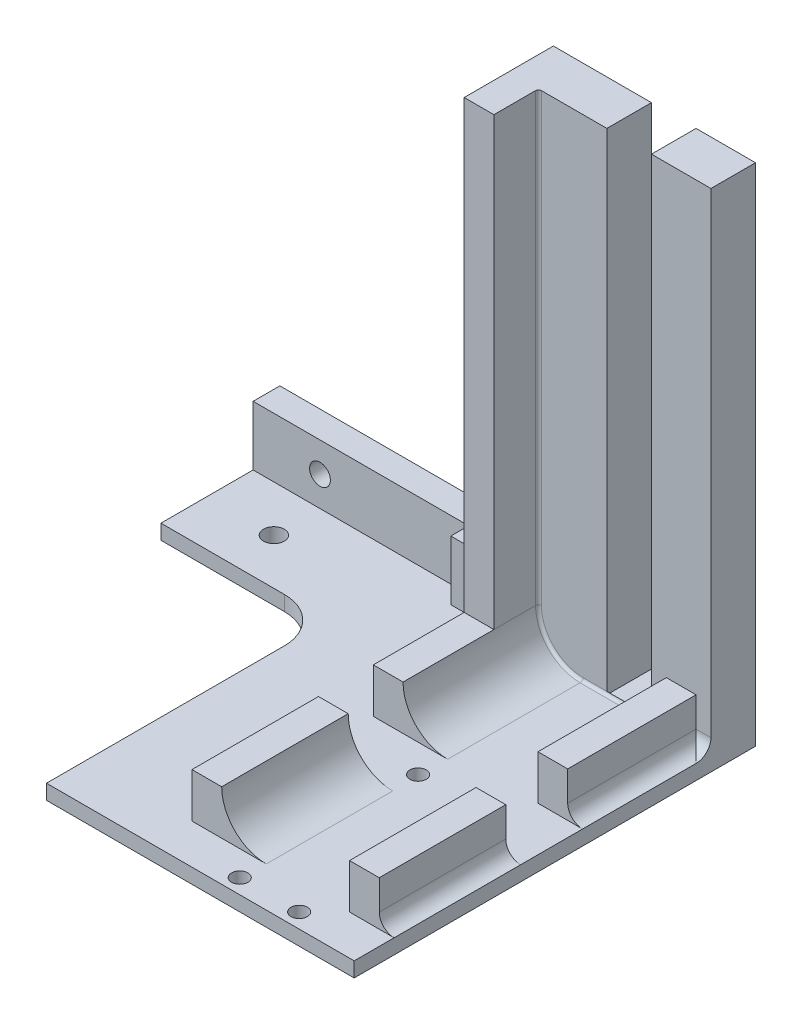
SolidWorks part; units mm, degrees
ref_plane "Front Plane" through (0, 0, 0) normal (0, 0, 1) x (1, 0, 0)
ref_plane "Top Plane" through (0, 0, 0) normal (0, 1, 0) x (1, 0, 0)
ref_plane "Right Plane" through (0, 0, 0) normal (1, 0, 0) x (0, 0, -1)
sketch "profile" plane through (0, 0, 0) normal (0, 0, 1) x (1, 0, 0)
  line L0 (11.8803, 7.4874) -> (14.5, 7.4874)
  line L1 (-5.5, 6.9749) -> (-7.8749, 4.6)
  line L2 (-7.8749, 4.6) -> (-12.1251, 4.6)
  line L3 (-12.1251, 4.6) -> (-14.5, 6.9749)
  line L4 (-8.1197, 7.4874) -> (-5.5, 7.4874)
  line L5 (-14.5, 6.9749) -> (-15.0126, 7.4874)
  line L6 (14.5, 6.9749) -> (12.1251, 4.6)
  line L7 (12.1251, 4.6) -> (7.8749, 4.6)
  line L8 (7.8749, 4.6) -> (5.5, 6.9749)
  line L9 (-14.7464, 10.3536) -> (-5.2536, 10.3536)
  line L10 (-14.5, 7.4874) -> (-11.8803, 7.4874)
  line L11 (5.5, 7.4874) -> (8.5334, 7.4874)
  line L12 (5.6673, 10.3536) -> (14.7464, 10.3536)
  line L13 (-15.0126, 7.4874) -> (-14.5, 7.4874)
  line L14 (-5.5, 6.9749) -> (-4.9874, 7.4874)
  line L15 (-4.9874, 7.4874) -> (-5.5, 7.4874)
  line L16 (5.5, 6.9749) -> (4.9874, 7.4874)
  line L17 (4.9874, 7.4874) -> (5.5, 7.4874)
  line L18 (14.5, 6.9749) -> (15.0126, 7.4874)
  line L19 (15.0126, 7.4874) -> (14.5, 7.4874)
  line L20 (-12.7464, 8.3536) -> (-14.7464, 10.3536)
  line L21 (-5.2536, 10.3536) -> (-7.2536, 8.3536)
  line L22 (7.6673, 8.3536) -> (5.6673, 10.3536)
  line L23 (14.7464, 10.3536) -> (12.7464, 8.3536)
  line L24 (-12.7464, 8.3536) -> (-11.8803, 7.4874)
  line L25 (-7.2536, 8.3536) -> (-8.1197, 7.4874)
  line L26 (7.6673, 8.3536) -> (8.5334, 7.4874)
  line L27 (12.7464, 8.3536) -> (11.8803, 7.4874)
  line L28 (-14.7464, 10.3536) -> (-20, 10.3536)
  line L29 (-20, 10.3536) -> (-20, 15.3536)
  line L30 (-20, 15.3536) -> (20, 15.3536)
  line L31 (20, 15.3536) -> (20, 10.3536)
  line L32 (20, 10.3536) -> (14.7464, 10.3536)
  line L33 (-5.2536, 10.3536) -> (5.6673, 10.3536)
  point P0 (-10, 4.6)
  point P1 (10, 4.6)
  dimension "D1" = 4.2503
  dimension "D2" = 5.7536
  dimension "D3" = 15.7497
  dimension "D4" = 20
  dimension "D5" = 5
extrude "Boss-Extrude1" add sketch "profile" along normal blind 250 contours L9 L33 L12 L32 L31 L30 L29 L28 region at (0, 12.8536, 0)
extrude "Boss-Extrude2" add sketch "Sketch1<3>" along normal blind 50 separate body contours L25 L21 L9 L20 L24 L10 L13 L5 L3 L2 L1 L14 L15 L4 | L27 L23 L12 L22 L26 L11 L17 L16 L8 L7 L6 L18 L19 L0 region at (10.0959, 7.5838, 0) region at (-10, 7.6238, 0)
sketch "Sketch1<3>" plane through (0, 0, 0) normal (0, 0, 1) x (1, 0, 0) same geometry as "profile"
pattern_linear "LPattern1" count 4 spacing 60 along (0, 0, 1) of "Boss-Extrude2"
sketch "Sketch2" plane through (0, 10.3536, 0) normal (0, -1, 0) x (1, 0, 0)
  line L0 (10, 250) -> (10, 0) construction
  line L1 (-20, 250) -> (20, 250) construction
  line L2 (12.1251, 0) -> (7.8749, 0) construction
  line L3 (-10, 230) -> (-10, 0) construction
  line L4 (-7.8749, 230) -> (-12.1251, 230) construction
  line L5 (-7.8749, 0) -> (-12.1251, 0) construction
  line L6 (-7.8749, 180) -> (-7.8749, 170) construction
  line L7 (-7.8749, 180) -> (-12.1251, 180) construction
  circle A0 centre (-10, 175) radius 2.75
  circle A1 centre (10, 175) radius 2.75
  circle A2 centre (-10, 115) radius 2.75
  circle A3 centre (10, 115) radius 2.75
  circle A4 centre (-10, 55) radius 2.75
  circle A5 centre (10, 55) radius 2.75
  point P21 (-7.8749, 175)
  dimension "D1" = 5.5
  dimension "D2" = 3
extrude "Cut-Extrude1" cut sketch "Sketch2" against normal through all
sketch "upper_acrylic_supp" plane through (0, 15.3536, 0) normal (0, 1, 0) x (1, 0, 0)
  line L0 (-20, 0) -> (20, 0) construction
  line L1 (-20, -250) -> (-34.5, -250) construction
  line L2 (-20, -250) -> (-20, 0) construction
  line L3 (-20, 0) -> (-34.5, 0) construction
  line L4 (-34.5, -250) -> (-34.5, 0) construction
  line L6 (-34.5, -250) -> (-24.5, -250)
  line L7 (-34.5, -250) -> (-34.5, -183.9264)
  line L8 (-34.5, -183.9264) -> (-24.5, -183.9264)
  line L9 (-24.5, -250) -> (-24.5, -183.9264)
  line L10 (-34.5, -165.3527) -> (-24.5, -165.3527)
  line L11 (-34.5, -165.3527) -> (-34.5, -123.8775)
  line L12 (-34.5, -123.8775) -> (-24.5, -123.8775)
  line L13 (-24.5, -165.3527) -> (-24.5, -123.8775)
  line L14 (-34.5, -106.5661) -> (-24.5, -106.5661)
  line L15 (-34.5, -106.5661) -> (-34.5, -64.0089)
  line L16 (-34.5, -64.0089) -> (-24.5, -64.0089)
  line L17 (-24.5, -106.5661) -> (-24.5, -64.0089)
  line L18 (-34.5, -45.5583) -> (-24.5, -45.5583)
  line L19 (-34.5, -45.5583) -> (-34.5, 0)
  line L20 (-34.5, 0) -> (-24.5, 0)
  line L21 (-24.5, -45.5583) -> (-24.5, 0)
  line L22 (-20, -250) -> (-40, -250)
  line L23 (-20, -250) -> (-20, 0)
  line L24 (-20, 0) -> (-40, 0)
  line L25 (-40, -250) -> (-40, 0)
  line M21 (-20, 0) -> (-20, -250)
  dimension "D1" = 5.5
  dimension "D2" = 10
  dimension "D3" = 20
extrude "Boss-Extrude3" add sketch "upper_acrylic_supp" against normal blind 5 contours L25 L22 L24 L21 L18 L19 L17 L14 L15 L16 L13 L10 L11 L12 L9 L6 L7 L8 M21 | L14 L17 L16 L15 | L10 L13 L12 L11 | L6 L9 L8 L7 | L18 L21 L20 L19 region at (-29.5, 15.3536, 216.9632) region at (-30.3215, 15.3536, 123.2164) region at (-29.5, 15.3536, 22.7792) region at (-29.5, 15.3536, 144.6151) region at (-29.5, 15.3536, 85.2875)
extrude "Boss-Extrude4" add sketch "upper_acrylic_supp<3>" along normal blind 15 contours L6 L9 L8 L7 | L10 L13 L12 L11 | L14 L17 L16 L15 | L18 L21 L20 L19 region at (-29.5, 15.3536, 216.9632) region at (-29.5, 15.3536, 22.7792) region at (-29.5, 15.3536, 144.6151) region at (-29.5, 15.3536, 85.2875)
sketch "upper_acrylic_supp<3>" plane through (0, 15.3536, 0) normal (0, 1, 0) x (1, 0, 0) same geometry as "upper_acrylic_supp"
fillet "Fillet1" radius 15 4 edges at (-24.5, 15.3536, 22.7792) (-24.5, 15.3536, 85.2875) (-24.5, 15.3536, 144.6151) (-24.5, 15.3536, 216.9632)
sketch "Sketch4" plane through (0, 15.3536, 0) normal (0, 1, 0) x (1, 0, 0)
  line L0 (20, -250) -> (20, 0) construction
  line L1 (-40, -250) -> (20, -250)
  line L2 (-40, -250) -> (-40, -265)
  line L3 (-40, -265) -> (20, -265)
  line L4 (20, -250) -> (20, -265)
  line L5 (-40, 0) -> (20, 0)
  line L6 (-40, 0) -> (-40, 15)
  line L7 (-40, 15) -> (20, 15)
  line L8 (20, 0) -> (20, 15)
  line L10 (-34.5, -265) -> (-34.5, 15) construction
  dimension "D1" = 15
  dimension "D2" = 15
extrude "Boss-Extrude5" add sketch "Sketch4" along normal mid plane 10
extrude "Boss-Extrude6" add sketch "Sketch4<3>" along normal blind 60
sketch "Sketch4<3>" plane through (0, 15.3536, 0) normal (0, 1, 0) x (1, 0, 0) same geometry as "Sketch4"
sketch "Sketch5" plane through (0, 0, 250) normal (0, 0, -1) x (-1, 0, 0)
  line L0 (-20, 75.3536) -> (40, 75.3536) construction
  line L1 (40, 15.3536) -> (34.5, 15.3536)
  line L2 (40, 15.3536) -> (40, 75.3536)
  line L3 (40, 75.3536) -> (34.5, 75.3536)
  line L4 (34.5, 15.3536) -> (34.5, 75.3536)
  line L6 (34.5, 15.3536) -> (24.5, 15.3536)
  line L7 (34.5, 15.3536) -> (34.5, 75.3536)
  line L8 (34.5, 75.3536) -> (24.5, 75.3536)
  line L9 (24.5, 15.3536) -> (24.5, 75.3536)
  line M5 (40, 75.3536) -> (-20, 75.3536)
  line M9 (24.5, 30.3536) -> (34.5, 30.3536)
  dimension "D1" = 5.5
  dimension "D2" = 10
extrude "Boss-Extrude7" add sketch "Sketch5" along normal blind 15 contours L9 L4 M9 M5 region at (-29.5, 52.8536, 250)
extrude "Boss-Extrude8" add sketch "Sketch5<3>" against normal blind 15 from surface contours L9 L4 M9 M5 region at (-29.5, 52.8536, 250) starting at face at (-18.2633, 33.7152, 0)
sketch "Sketch5<3>" plane through (0, 0, 250) normal (0, 0, -1) x (-1, 0, 0) same geometry as "Sketch5"
fillet "Fillet2" radius 1 6 edges at (5.25, 15.3536, 0) (-20.1066, 19.747, 0) (5.25, 15.3536, 250) (-20.1066, 19.747, 250) (-24.5, 52.8536, 0) (-24.5, 52.8536, 250)
sketch "Sketch6" plane through (-40, 0, 0) normal (-1, 0, 0) x (0, 0, 1)
  line L1 (250, 15.3536) -> (256, 15.3536)
  line L2 (250, 15.3536) -> (250, 75.3536)
  line L3 (250, 75.3536) -> (256, 75.3536)
  line L4 (256, 15.3536) -> (256, 75.3536)
  line L6 (0, 15.3536) -> (-6, 15.3536)
  line L7 (0, 15.3536) -> (0, 75.3536)
  line L8 (0, 75.3536) -> (-6, 75.3536)
  line L9 (-6, 15.3536) -> (-6, 75.3536)
  dimension "D1" = 6
  dimension "D2" = 6
extrude "Cut-Extrude2" cut sketch "Sketch6" against normal blind 6
sketch "Sketch7" plane through (-40, 0, 0) normal (-1, 0, 0) x (0, 0, 1)
  line L8 (265, 75.3536) -> (256, 75.3536)
  line L9 (256, 75.3536) -> (256, 15.3536)
  line L10 (256, 15.3536) -> (-6, 15.3536)
  line L11 (-6, 15.3536) -> (-6, 75.3536)
  line L12 (-6, 75.3536) -> (-15, 75.3536)
  line L13 (-15, 75.3536) -> (-15, 10.3536)
  line L14 (-15, 10.3536) -> (265, 10.3536)
  line L15 (265, 10.3536) -> (265, 75.3536)
  line L16 (265, 75.3536) -> (256, 75.3536)
  line L17 (256, 75.3536) -> (256, 15.3536)
  line L18 (256, 15.3536) -> (-6, 15.3536)
  line L19 (-6, 15.3536) -> (-6, 75.3536)
  line L20 (-6, 75.3536) -> (-15, 75.3536)
  line L21 (-15, 75.3536) -> (-15, 10.3536)
  line L22 (-15, 10.3536) -> (265, 10.3536)
  line L23 (265, 10.3536) -> (265, 75.3536)
  dimension "D1" = 0
extrude "Boss-Extrude9" add sketch "Sketch7" along normal blind 30
sketch "Sketch8" plane through (-70, 0, 0) normal (-1, 0, 0) x (0, 0, 1)
  line L0 (-15, 10.3536) -> (265, 10.3536) construction
  line L1 (-44.3745, 35.3536) -> (289.2282, 35.3536)
  line L2 (-44.3745, 35.3536) -> (-44.3745, 94.3849)
  line L3 (-44.3745, 94.3849) -> (289.2282, 94.3849)
  line L4 (289.2282, 35.3536) -> (289.2282, 94.3849)
  dimension "D1" = 25
extrude "Cut-Extrude3" cut sketch "Sketch8" against normal blind 150
sketch "Sketch9" plane through (-34, 0, 0) normal (-1, 0, 0) x (0, 0, 1)
  line L4 (256, 15.3536) -> (256, 35.3536)
  line L5 (256, 35.3536) -> (250, 35.3536)
  line L6 (250, 35.3536) -> (250, 15.3536)
  line L7 (250, 15.3536) -> (256, 15.3536)
  line L8 (256, 15.3536) -> (256, 35.3536)
  line L9 (256, 35.3536) -> (250, 35.3536)
  line L10 (250, 35.3536) -> (250, 15.3536)
  line L11 (250, 15.3536) -> (256, 15.3536)
  line L12 (0, 35.3536) -> (-6, 35.3536)
  line L13 (-6, 35.3536) -> (-6, 15.3536)
  line L14 (-6, 15.3536) -> (0, 15.3536)
  line L15 (0, 15.3536) -> (0, 35.3536)
  line L16 (0, 35.3536) -> (-6, 35.3536)
  line L17 (-6, 35.3536) -> (-6, 15.3536)
  line L18 (-6, 15.3536) -> (0, 15.3536)
  line L19 (0, 15.3536) -> (0, 35.3536)
  dimension "D1" = 0
  dimension "D2" = 0
extrude "cloth_escape_gap" add sketch "Sketch9" along normal blind 20
sketch "Sketch11" plane through (-70, 0, 0) normal (-1, 0, 0) x (0, 0, 1)
  line L0 (256, 35.3536) -> (256, 15.3536) construction
  line L1 (-15, 35.3536) -> (-6, 35.3536)
  line L2 (-15, 35.3536) -> (-15, 15.3536)
  line L3 (-15, 15.3536) -> (-6, 15.3536)
  line L4 (-6, 35.3536) -> (-6, 15.3536)
  line L5 (265, 35.3536) -> (256, 35.3536)
  line L6 (265, 35.3536) -> (265, 15.3536)
  line L7 (265, 15.3536) -> (256, 15.3536)
  line L8 (256, 35.3536) -> (256, 15.3536)
  line L9 (256, 15.3536) -> (256, 35.3536) construction
extrude "Boss-Extrude11" add sketch "Sketch11" along normal blind 100
sketch "Sketch12" plane through (0, 10.3536, 0) normal (0, -1, 0) x (1, 0, 0)
  line L0 (-70, -15) -> (-170, -10.5)
  line L1 (-170, -15) -> (-170, -6) construction
  line L2 (-170, -10.5) -> (-170, -15)
  line L3 (-170, -15) -> (-70, -15) construction
  line L4 (-170, -15) -> (-70, -15)
  line L5 (-70, 265) -> (-170, 260.5)
  line L6 (-170, 256) -> (-170, 265) construction
  line L7 (-170, 260.5) -> (-170, 265)
  line L8 (-170, 265) -> (-70, 265)
extrude "Cut-Extrude4" cut sketch "Sketch12" against normal blind 68 contours L8 L7 L5 | L0 L2 L4 region at (-136.6667, 10.3536, 263.5)
sketch "Sketch13" plane through (-70, 0, 0) normal (-1, 0, 0) x (0, 0, 1)
  line L0 (256, 15.3536) -> (265, 15.3536) construction
  line L1 (-15, 10.3536) -> (25, 10.3536)
  line L2 (-15, 10.3536) -> (-15, 15.3536)
  line L3 (-15, 15.3536) -> (25, 15.3536)
  line L4 (25, 10.3536) -> (25, 15.3536)
  line L5 (265, 10.3536) -> (225, 10.3536)
  line L6 (265, 10.3536) -> (265, 15.3536)
  line L7 (265, 15.3536) -> (225, 15.3536)
  line L8 (225, 10.3536) -> (225, 15.3536)
  line L9 (256, 15.3536) -> (-6, 15.3536) construction
  dimension "D1" = 40
  dimension "D2" = 40
extrude "Boss-Extrude13" add sketch "Sketch13" along normal blind 100
sketch "Sketch14" plane through (0, 15.3536, 0) normal (0, 1, 0) x (1, 0, 0)
  line L3 (-70, -265) -> (-170, -260.5)
  line L4 (-170, -260.5) -> (-170, -265)
  line L5 (-170, -265) -> (-70, -265)
  line L6 (-70, -265) -> (-170, -260.5)
  line L7 (-170, -260.5) -> (-170, -265)
  line L8 (-170, -265) -> (-70, -265)
  line L9 (-170, 15) -> (-170, 10.5)
  line L10 (-170, 10.5) -> (-70, 15)
  line L11 (-70, 15) -> (-170, 15)
  line L12 (-170, 15) -> (-170, 10.5)
  line L13 (-170, 10.5) -> (-70, 15)
  line L14 (-70, 15) -> (-170, 15)
  dimension "D1" = 0
  dimension "D2" = 0
extrude "Cut-Extrude5" cut sketch "Sketch14" against normal blind 100
fillet "Fillet3" radius 15 2 edges at (-70, 12.8536, 25) (-70, 12.8536, 225)
sketch "Sketch16" plane through (0, 15.3536, 0) normal (0, 1, 0) x (1, 0, 0)
  line L0 (20, -1) -> (-9.5, -1) construction
  line L1 (-34.5, -235) -> (18.5, -235) construction
  line L2 (-34.5, -235) -> (-34.5, -1) construction
  line L3 (-34.5, -1) -> (18.5, -1) construction
  line L4 (18.5, -235) -> (18.5, -1) construction
  line L5 (20, -265) -> (-70, -265) construction
  line L6 (18.5, -265) -> (33.5, -265)
  line L7 (18.5, -265) -> (18.5, 15)
  line L8 (18.5, 15) -> (33.5, 15)
  line L9 (33.5, -265) -> (33.5, 15)
  line L10 (-70, 15) -> (20, 15) construction
  line L11 (18.5, -250) -> (33.5, -250)
  line L12 (18.5, 0) -> (33.5, 0)
  line L13 (-23.5, -250) -> (20, -250) construction
  line L14 (-9.5, 0) -> (20, 0) construction
  line L15 (18.5, -250) -> (28.5, -250)
  line L16 (28.5, -250) -> (28.5, -183.9264)
  line L17 (28.5, 0) -> (18.5, 0)
  line L18 (18.5, -183.9264) -> (28.5, -183.9264)
  line L19 (18.5, -165.3527) -> (28.5, -165.3527)
  line L20 (18.5, -123.8775) -> (28.5, -123.8775)
  line L21 (18.5, -106.5661) -> (28.5, -106.5661)
  line L22 (18.5, -64.0089) -> (28.5, -64.0089)
  line L23 (18.5, -43.1778) -> (28.5, -43.1778)
  line L24 (-34.5, -165.3527) -> (-9.5, -165.3527) construction
  line L25 (-34.5, -183.9264) -> (-9.5, -183.9264) construction
  line L26 (-34.5, -106.5661) -> (-9.5, -106.5661) construction
  line L27 (-34.5, -123.8775) -> (-9.5, -123.8775) construction
  line L28 (-9.5, -64.0089) -> (-24.5, -64.0089) construction
  line L30 (28.5, -165.3527) -> (28.5, -123.8775)
  line L31 (28.5, -106.5661) -> (28.5, -64.0089)
  line L32 (28.5, -43.1778) -> (28.5, 0)
  line M38 (-9.5, -249) -> (20, -249)
  line M39 (20, -249) -> (20, -1)
  line M40 (20, -1) -> (-9.5, -1)
  dimension "D1" = 53
  dimension "D2" = 15
  dimension "D3" = 10
extrude "Boss-Extrude14" add sketch "Sketch16" along direction (0, -1, 0) on the side of the normal up to surface (20 mm away) from surface contours L7 L12 L9 L8 | L11 L7 L6 L9 region at (26, 15.3536, 257.5) region at (26, 15.3536, -7.5) up to face at (-51.6423, 35.3536, 251.8089) starting at face at (-10, 10.3536, 25)
extrude "Cut-Extrude6" cut sketch "Sketch16<5>" against normal blind 10 and the other way blind 30 contours L11 L7 L6 L9 | L32 L23 L22 L31 L21 L20 L30 L19 L18 L16 L11 L9 L12 M39 | L19 L30 L20 M39 | L21 L31 L22 M39 | L23 L32 L12 L7 M40 M39 | L7 L12 L9 L8 | L7 L23 M39 M40 | L23 L7 L22 M39 | L22 L7 L21 M39 | L21 L7 L20 M39 | L20 L7 L19 M39 | L19 L7 L18 M39 | L18 L7 M38 M39 | L18 L7 L11 L16 M39 M38 region at (26, 15.3536, 257.5) region at (24.2367, 15.3536, 217.0499) region at (29.1213, 15.3536, 121.3942) region at (19.25, 15.3536, 216.4632) region at (26, 15.3536, -7.5) region at (19.25, 15.3536, 174.6396) region at (24.2296, 15.3536, 21.5031) region at (19.25, 15.3536, 144.6151) region at (19.25, 15.3536, 115.2218) region at (24.25, 15.3536, 144.6151) region at (19.25, 15.3536, 22.0889) region at (19.25, 15.3536, 53.5934) region at (19.25, 15.3536, 85.2875) region at (24.25, 15.3536, 85.2875)
sketch "Sketch16<5>" plane through (0, 15.3536, 0) normal (0, 1, 0) x (1, 0, 0) same geometry as "Sketch16"
extrude "Boss-Extrude15" add sketch "Sketch16<6>" against normal up to surface (5 mm away) contours L32 L23 L22 L31 L21 L20 L30 L19 L18 L16 L11 L9 L12 M39 | L18 L7 L11 L16 M39 M38 | L11 L7 L6 L9 | L19 L30 L20 M39 | L21 L31 L22 M39 | L23 L32 L12 L7 M40 M39 | L7 L12 L9 L8 | L7 L23 M39 M40 | L23 L7 L22 M39 | L22 L7 L21 M39 | L21 L7 L20 M39 | L20 L7 L19 M39 | L19 L7 L18 M39 | L18 L7 M38 M39 region at (26, 15.3536, 257.5) region at (24.2367, 15.3536, 217.0499) region at (29.1213, 15.3536, 121.3942) region at (19.25, 15.3536, 216.4632) region at (26, 15.3536, -7.5) region at (19.25, 15.3536, 174.6396) region at (24.2296, 15.3536, 21.5031) region at (19.25, 15.3536, 144.6151) region at (19.25, 15.3536, 115.2218) region at (24.25, 15.3536, 144.6151) region at (19.25, 15.3536, 22.0889) region at (19.25, 15.3536, 53.5934) region at (19.25, 15.3536, 85.2875) region at (24.25, 15.3536, 85.2875) up to face at (-90.5656, 10.3536, 125)
sketch "Sketch16<6>" plane through (0, 15.3536, 0) normal (0, 1, 0) x (1, 0, 0) same geometry as "Sketch16"
extrude "Boss-Extrude16" add sketch "Sketch16<7>" along normal up to surface (20 mm away) contours L11 L7 L6 L9 | L7 L12 L9 L8 region at (26, 15.3536, 257.5) region at (26, 15.3536, -7.5) up to face at (-51.8923, 35.3536, 251.8089)
sketch "Sketch16<7>" plane through (0, 15.3536, 0) normal (0, 1, 0) x (1, 0, 0) same geometry as "Sketch16"
extrude "Boss-Extrude17" add sketch "Sketch16<8>" along normal up to surface (15 mm away) contours L18 L7 L11 L16 M39 M38 | L19 L30 L20 M39 | L21 L31 L22 M39 | L23 L32 L12 L7 M40 M39 | L7 L23 M39 M40 | L22 L7 L21 M39 | L20 L7 L19 M39 | L18 L7 M38 M39 region at (24.2367, 15.3536, 217.0499) region at (19.25, 15.3536, 216.4632) region at (24.2296, 15.3536, 21.5031) region at (19.25, 15.3536, 144.6151) region at (24.25, 15.3536, 144.6151) region at (19.25, 15.3536, 22.0889) region at (19.25, 15.3536, 85.2875) region at (24.25, 15.3536, 85.2875) up to face at (-29.5, 30.3536, 209.4632)
sketch "Sketch16<8>" plane through (0, 15.3536, 0) normal (0, 1, 0) x (1, 0, 0) same geometry as "Sketch16"
extrude "Boss-Extrude18" add sketch "Sketch14<2>" along normal up to surface (20 mm away) and the other way up to surface (5 mm away) up to face at (-49.3923, 35.3536, -1.8089) other way up to face at (-88.0656, 10.3536, 125)
sketch "Sketch14<2>" plane through (0, 15.3536, 0) normal (0, 1, 0) x (1, 0, 0) same geometry as "Sketch14"
fillet "Fillet4" radius 5 6 edges at (31, 15.3536, 250) (31, 15.3536, 0) (28.5, 15.3536, 21.5889) (28.5, 15.3536, 85.2875) (28.5, 15.3536, 144.6151) (28.5, 15.3536, 216.9632)
sketch "Sketch18" plane through (0, 35.3536, 0) normal (0, 1, 0) x (1, 0, 0)
  line L2 (-34.5, -250) -> (-34.5, -265)
  line L3 (-34.5, 15) -> (-34.5, 0)
  line L12 (-23.5, 0) -> (33.5, 0)
  line L13 (33.5, 0) -> (33.5, 15)
  line L14 (33.5, 15) -> (-170, 15)
  line L15 (-170, 15) -> (-170, 6)
  line L30 (-170, 6) -> (-54, 6)
  line L32 (-54, 6) -> (-54, 0)
  line L38 (-54, 0) -> (-34.5, 0)
  line L39 (-34.5, 0) -> (-34.5, -15)
  line L50 (-34.5, -15) -> (-24.5, -15)
  line L51 (-24.5, -15) -> (-24.5, -1)
  line L52 (-23.5, 0) -> (33.5, 0)
  line L53 (33.5, 0) -> (33.5, 15)
  line L54 (33.5, 15) -> (-34.5, 15)
  line L59 (-34.5, 0) -> (-34.5, -15)
  line L60 (-34.5, -15) -> (-24.5, -15)
  line L61 (-24.5, -15) -> (-24.5, -1)
  line L62 (-170, -265) -> (33.5, -265)
  line L63 (33.5, -265) -> (33.5, -250)
  line L64 (33.5, -250) -> (-23.5, -250)
  line L65 (-24.5, -249) -> (-24.5, -235)
  line L66 (-24.5, -235) -> (-34.5, -235)
  line L67 (-34.5, -235) -> (-34.5, -250)
  line L68 (-34.5, -250) -> (-54, -250)
  line L69 (-54, -250) -> (-54, -256)
  line L70 (-54, -256) -> (-170, -256)
  line L71 (-170, -256) -> (-170, -265)
  line L72 (-34.5, -265) -> (33.5, -265)
  line L73 (33.5, -265) -> (33.5, -250)
  line L74 (33.5, -250) -> (-23.5, -250)
  line L75 (-24.5, -249) -> (-24.5, -235)
  line L76 (-24.5, -235) -> (-34.5, -235)
  line L77 (-34.5, -235) -> (-34.5, -250)
  arc A5 (-23.5, 0) -> (-24.5, -1) centre (-23.5, -1) ccw
  arc A6 (-23.5, 0) -> (-24.5, -1) centre (-23.5, -1) ccw
  arc A7 (-24.5, -249) -> (-23.5, -250) centre (-23.5, -249) ccw
  arc A8 (-24.5, -249) -> (-23.5, -250) centre (-23.5, -249) ccw
  dimension "D1" = 0
  dimension "D2" = 0
extrude "Boss-Extrude21" add sketch "Sketch18" along normal blind 170 from surface starting at face at (-91.6787, 10.3536, 125)
sketch "Sketch19" plane through (0, 15.3536, 0) normal (0, 1, 0) x (1, 0, 0)
  line L0 (-170, -25) -> (-170, 6) construction
  line L1 (-70, -125) -> (-196.5165, -125) construction
  line L2 (-70, -210) -> (-70, -40) construction
  circle A0 centre (-154, -9.5) radius 3.5
  circle A1 centre (-104, -9.5) radius 3.5
  circle A2 centre (-104, -240.5) radius 3.5
  circle A3 centre (-154, -240.5) radius 3.5
  point P6 (-170, -9.5)
  dimension "D1" = 7
  dimension "D2" = 50
  dimension "D3" = 50
extrude "Cut-Extrude7" cut sketch "Sketch19" against normal blind 10
sketch "Sketch20" plane through (0, 0, 256) normal (0, 0, -1) x (-1, 0, 0)
  line L4 (34.5, 35.3536) -> (34.5, 15.3536)
  line L5 (34.5, 15.3536) -> (54, 15.3536)
  line L6 (54, 15.3536) -> (54, 35.3536)
  line L7 (54, 35.3536) -> (34.5, 35.3536)
  line L8 (34.5, 35.3536) -> (34.5, 15.3536)
  line L9 (34.5, 15.3536) -> (54, 15.3536)
  line L10 (54, 15.3536) -> (54, 35.3536)
  line L11 (54, 35.3536) -> (34.5, 35.3536)
  circle A0 centre (104, 25.3536) radius 3.5
  circle A1 centre (154, 25.3536) radius 3.5
  point P8 (54, 25.3536)
  dimension "D3" = 7
  dimension "D2" = 50
  dimension "D4" = 50
  dimension "D1" = 0
extrude "Cut-Extrude8" cut sketch "Sketch20" against normal blind 10 and the other way blind 355 contours A0 | A1 region at (-104, 25.3536, 256) region at (-154, 25.3536, 256)
sketch "Sketch21" plane through (0, 0, 0) normal (0, 0, 1) x (1, 0, 0)
  line L1 (13.5, 15.3536) -> (-1.5, 15.3536)
  line L2 (13.5, 15.3536) -> (13.5, 212.8546)
  line L3 (13.5, 212.8546) -> (-1.5, 212.8546)
  line L4 (-1.5, 15.3536) -> (-1.5, 212.8546)
  line L6 (18.5, 15.3536) -> (-9.5, 15.3536) construction
  line L7 (18.5, 30.3536) -> (18.5, 16.3536) construction
  dimension "D1" = 15
  dimension "D2" = 5
extrude "Cut-Extrude9" cut sketch "Sketch21" against normal blind 130
sketch "Sketch22" plane through (0, 0, 0) normal (0, 1, 0) x (1, 0, 0)
  line L5 (33.5, 15) -> (-126.5, 15)
  line L6 (33.5, 15) -> (33.5, -120)
  line L7 (33.5, -120) -> (-126.5, -120)
  line L8 (-126.5, 15) -> (-126.5, -120)
  line L11 (33.5, -265) -> (-126.5, -265)
  line L12 (33.5, -265) -> (33.5, -130)
  line L13 (33.5, -130) -> (-126.5, -130)
  line L14 (-126.5, -265) -> (-126.5, -130)
  line L15 (-126.5, -120) -> (-126.5, -130)
  line L16 (33.5, -120) -> (33.5, -130)
  line L19 (-126.5, 15) -> (-186.5, 15)
  line L20 (-126.5, 15) -> (-126.5, -265)
  line L21 (-126.5, -265) -> (-186.5, -265)
  line L22 (-186.5, 15) -> (-186.5, -265)
  dimension "D1" = 160
  dimension "D2" = 135
  dimension "D3" = 135
  dimension "D4" = 60
extrude "Cut-Extrude10" cut sketch "Sketch22" along normal blind 270 contours L14 L11 L12 L13 | L19 L22 L21 L14 L15 L8 | L16 L7 L15 L13 region at (-156.5, 0, 125) region at (-46.5, 0, 125) region at (-46.5, 0, 197.5)
